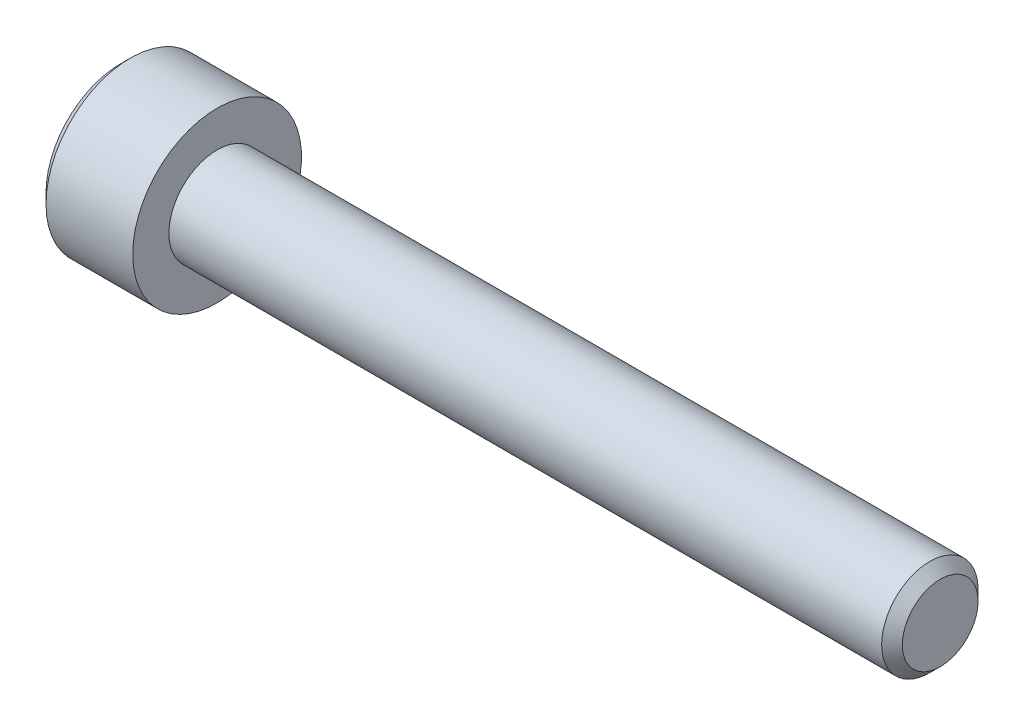
SolidWorks part; units mm, degrees
ref_plane "Front Plane" through (0, 0, 0) normal (0, 0, 1) x (1, 0, 0)
ref_plane "Top Plane" through (0, 0, 0) normal (0, 1, 0) x (1, 0, 0)
ref_plane "Right Plane" through (0, 0, 0) normal (1, 0, 0) x (0, 0, -1)
ref_plane "Plane1" through (1, 0, 0) normal (1, 0, 0) x (0, 0, -1)
ref_axis "Axis_X" through (-5.7, 0, 0) along (1, 0, 0)
ref_axis "Axis_Y" through (0, 3.85, 0) along (0, -1, 0)
ref_axis "Axis_Z" through (0, 0, -3.85) along (0, 0, 1)
sketch "Sketch1" plane through (0, 0, 0) normal (0, 0, 1) x (1, 0, 0)
  line L0 (-4, 0) -> (30, 0)
  line L1 (30, 0) -> (30, -1.5705)
  line L2 (30, -1.5705) -> (29.5705, -2)
  line L3 (29.5705, -2) -> (0, -2)
  line L4 (0, -2) -> (0, -3.5)
  line L5 (0, -3.5) -> (-3.6, -3.5)
  line L6 (-3.6, -3.5) -> (-4, -3.1)
  line L7 (-4, -3.1) -> (-4, 0)
  line L8 (0, 0) -> (-4, 0) construction
  line L9 (30, 1.5705) -> (29.5705, 2) construction
  line L10 (-4, 3.1) -> (-3.6, 3.5) construction
  point P16 (29.3, -2)
  dimension "A" = 7
  dimension "E" = 4
  dimension "MSM_1" = 3.141
  dimension "MSM_2" = 45
  dimension "MSM_3" = 0.4
  dimension "L" = 30
  dimension "Pitch_1" = 0.7
revolve "Revolve1" add sketch "Sketch1" angle 360 about axis through (-5.7, 0, 0) along (1, 0, 0)
sketch "Sketch2" plane through (-4, 0, 0) normal (-1, 0, 0) x (0, 0, 1)
  line L1 (0, 1.7321) -> (-1.5, 0.866)
  line L2 (-1.5, 0.866) -> (-1.5, -0.866)
  line L3 (-1.5, -0.866) -> (0, -1.7321)
  line L4 (0, -1.7321) -> (1.5, -0.866)
  line L5 (1.5, -0.866) -> (1.5, 0.866)
  line L6 (1.5, 0.866) -> (0, 1.7321)
  circle A0 centre (0, 0) radius 1.5 construction
  dimension "B" = 3
extrude "Cut-Extrude1" cut sketch "Sketch2" against normal blind 2
ref_plane "Dim. B_s" through (30, 0, 0) normal (1, 0, 0) x (0, 0, -1)
sketch "Sketch3" plane through (0, 0, 0) normal (0, 0, 1) x (1, 0, 0)
  line L0 (0, 0) -> (30, 0) construction
  line L1 (30, -1.3128) -> (30, 1.3128) construction
  line L3 (29.99, 2) -> (30, 2)
  line L5 (29.99, 2) -> (29.99, 1.99)
  line L6 (29.99, 1.99) -> (30, 1.99)
  line L7 (30, 2) -> (30, 1.99)
  line L8 (27, 2) -> (27.01, 2)
  line L9 (27, 2) -> (27, 1.99)
  line L10 (27, 1.99) -> (27.01, 1.99)
  line L11 (27.01, 2) -> (27.01, 1.99)
  dimension "MSM_5" = 0.01
  dimension "A_s" = 3
revolve "Cut-Revolve1" [suppressed] cut sketch "Sketch3" angle 360 about L0
equation "\"Factor\"= 1.082532"
equation "\"ATD_1\"= 4.134"
equation "\"L_s\"= 10"
equation "\"L_s\"= IIF ( ( \"M\" = 12 and \"L\" > 50 ) , 36 , IIF ( ( \"M\" = 10 and \"L\" > 40 ) , 32 , IIF ( ( \"M\" = 8 and \"L\" > 35 ) , 28 , IIF ( ( \"M\" = 6 and \"L\" > 30 ) , 24 , IIF ( ( \"M\" = 5 and \"L\" > 25 ) , 22 , IIF ( ( \"M\" = 4 and \"L\" > 25 ) , 20 , IIF ( ( \"M\" = 3 and \"L\" > 20 ) , 18 , \"L\" ) ) ) ) ) ) )"
equation "\"A\"= IIF ( \"M\" = 12 , 18 , IIF ( \"M\" = 10 , 16 , IIF ( \"M\" = 8 , 13 , IIF ( \"M\" = 6 , 10 , IIF ( \"M\" = 5 , 8.5 , IIF ( \"M\" = 4 , 7 , IIF ( \"M\" = 3 , 5.5 , IIF ( \"M\" = 2.6 or \"M\" = 2.5 , 4.5 , 3.8 ) ) ) ) ) ) ) )"
equation "\"E\"= \"M\""
equation "\"B\"= IIF ( \"M\" = 12 , 10 , IIF ( \"M\" = 10 , 8 , IIF ( \"M\" = 8 , 6 , IIF ( \"M\" = 6 , 5 , IIF ( \"M\" = 5 , 4 , IIF ( \"M\" = 4 , 3 , IIF ( \"M\" = 3 , 2.5 , IIF ( \"M\" = 2.6 or \"M\" = 2.5 , 2 , 1.5 ) ) ) ) ) ) ) )"
equation "\"MSM_4\"= \"M\" * 0.5"
equation "\"MSM_1\"= IIF ( \"M\" = 12 , 9.853 , IIF ( \"M\" = 10 , 8.16 , IIF ( \"M\" = 8 , 6.466 , IIF ( \"M\" = 6 , 4.773 , IIF ( \"M\" = 5 , 4.019 , IIF ( \"M\" = 4 , 3.141 , IIF ( \"M\" = 3 , 2.387 , IIF ( \"M\" = 2.6 , 2.048 , IIF ( \"M\" = 2.5 , 1.948 , 1.509 ) ) ) ) ) ) ) ) )"
equation "\"MSM_2\"= 45"
equation "\"MSM_3\"= IIF ( \"M\" = 2.6 , 0.26 , \"E\" * 0.1 )"
equation "\"Thread1\" = IIF ( ( ( \"M\" = 12 ) and ( \"L\" > 50 ) ) or ( ( \"M\" = 10 ) and ( \"L\" > 40 ) ) or ( ( \"M\" = 8 ) and ( \"L\" > 35 ) ) or ( ( \"M\" = 6 ) and ( \"L\" > 30 ) ) or ( ( \"M\" = 5 ) and ( \"L\" > 25 ) ) or ( ( \"M\" = 4 ) and ( \"L\" > 25 ) ) or ( \"M\" = 3 ) and ( \"L\" > 2 ) , \"suppressed\" , \"unsuppressed\" )"
equation "\"Thread2\" = IIF ( ( ( \"M\" = 12 ) and ( \"L\" > 50 ) ) or ( ( \"M\" = 10 ) and ( \"L\" > 40 ) ) or ( ( \"M\" = 8 ) and ( \"L\" > 35 ) ) or ( ( \"M\" = 6 ) and ( \"L\" > 30 ) ) or ( ( \"M\" = 5 ) and ( \"L\" > 25 ) ) or ( ( \"M\" = 4 ) and ( \"L\" > 25 ) ) or ( \"M\" = 3 ) and ( \"L\" > 2 ) , \"unsuppressed\" , \"suppressed\" )"
equation "\"MSM_5\"= 0.01"
equation "\"Cut-Revolve1\"= IIF ( \"TYP\" = 2 , \"unsuppressed\" , \"suppressed\" )"
equation "\"Pitch_1\"= IIF ( \"M\" = 12 , 1.75 , IIF ( \"M\" = 10 , 1.5 , IIF ( \"M\" = 8 , 1.25 , IIF ( \"M\" = 6 , 1 , IIF ( \"M\" = 5 , 0.8 , IIF ( \"M\" = 4 , 0.7 , IIF ( \"M\" = 3 , 0.5 , IIF ( \"M\" = 2.6 or \"M\" = 2.5 , 0.45 , 0.4 ) ) ) ) ) ) ) )"
equation "\"ATD_2\"= round ( \"M\" - \"Factor\" * \"Pitch_1\" , 3 )"
